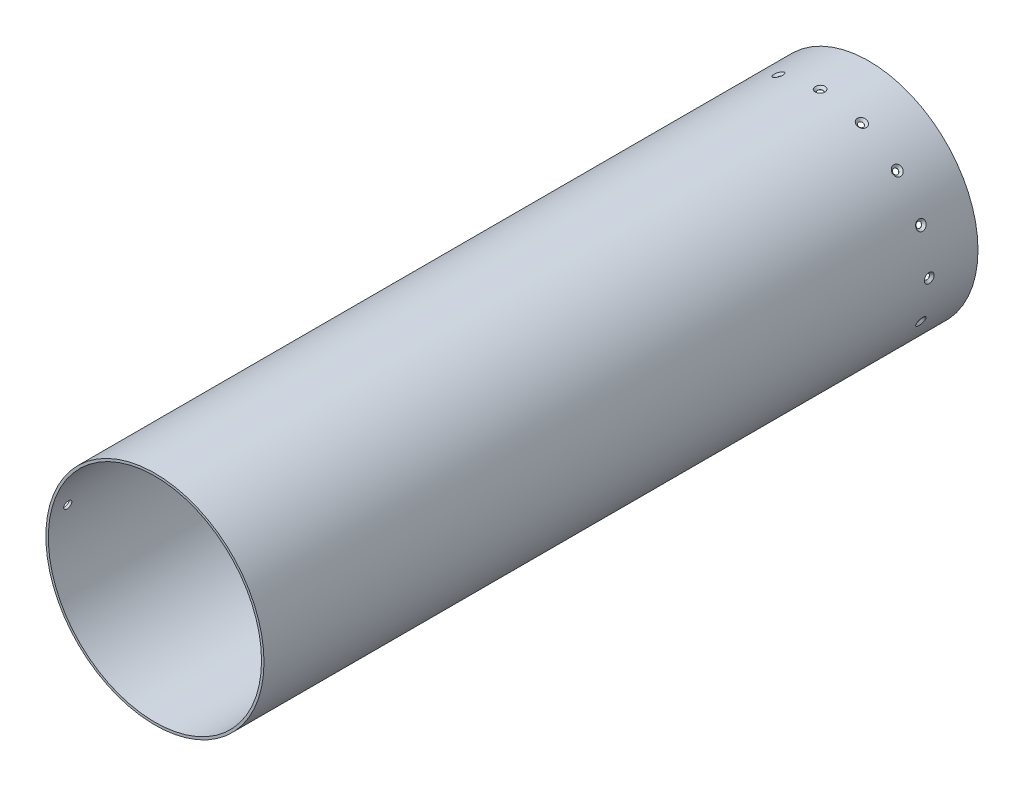
SolidWorks part; units mm, degrees
material "6061-T6 (SS)"
ref_plane "Front Plane" through (0, 0, 0) normal (0, 0, 1) x (1, 0, 0)
ref_plane "Top Plane" through (0, 0, 0) normal (0, 1, 0) x (1, 0, 0)
ref_plane "Right Plane" through (0, 0, 0) normal (1, 0, 0) x (0, 0, -1)
sketch "Sketch1" plane through (0, 0, 0) normal (0, 0, 1) x (1, 0, 0)
  circle A0 centre (0, 0) radius 69.85
  circle A1 centre (0, 0) radius 68.2625
  dimension "D1" = 139.7
  dimension "D2" = 1.5875
extrude "Extrude1" add sketch "Sketch1" along normal blind 457.2
ref_plane "Plane1" through (0, 0, 31.242) normal (0, 0, -1) x (-1, 0, 0)
sketch "Sketch2" plane through (0, 0, 31.242) normal (0, 0, -1) x (-1, 0, 0)
  line L0 (0, 0) -> (0, -69.85) construction
  circle A0 centre (0, 0) radius 69.85 construction
ref_plane "Plane2" through (0, -69.85, 31.242) normal (0, -1, 0) x (1, 0, 0)
hole_wizard "CSK for M3 Flat Head Machine Screw1" positions "Sketch5" profile "Sketch4" countersink size "M3" standard "Ansi Metric" end condition through all
sketch "Sketch5" plane through (0, -69.85, 31.242) normal (0, -1, 0) x (1, 0, 0)
  point P2 (0, 0)
sketch "Sketch4" plane through (0, -69.85, 31.242) normal (1, 0, 0) x (0, 0, -1)
  line L0 (0, 0) -> (0, 161.1134)
  line L1 (0, 161.1134) -> (1.7, 161.1134)
  line L2 (1.7, 161.1134) -> (1.7, 1.45)
  line L3 (1.7, 1.45) -> (3.15, 0)
  line L5 (3.15, 0) -> (0, 0)
  line L6 (-1.7, 1.45) -> (-3.15, 0) construction
  line L11 (0, -6.35) -> (0, 107.95) construction
  dimension "Thru Hole Dia." = 3.4
  dimension "Thru Hole Depth" = 161.1134
  dimension "Near C'Sink Dia." = 6.3
  dimension "Near C'Sink Angle" = 90
pattern_circular "CirPattern1" count 16 over 360 about axis through (0, 0, 457.2) along (0, 0, -1) of "CSK for M3 Flat Head Machine Screw1"
ref_plane "Plane3" through (0, 0, 446.0875) normal (0, 0, 1) x (1, 0, 0)
ref_plane "Plane5" through (0, 0, 0) normal (0.8315, 0.5556, 0) x (-0.5556, 0.8315, 0)
ref_plane "Plane7" through (0, 0, 0) normal (0.5556, -0.8315, 0) x (0.8315, 0.5556, 0)
ref_plane "Plane9" through (0, 0, 0) normal (-0.1951, -0.9808, 0) x (0.9808, -0.1951, 0)
sketch "Sketch7" plane through (0, 0, 457.2) normal (0, 0, 1) x (1, 0, 0)
  circle A0 centre (0, 0) radius 69.85 construction
  point P0 (69.85, 0)
ref_plane "Plane8" through (-68.5079, 13.6271, 228.6) normal (-0.9808, 0.1951, 0) x (0.1951, 0.9808, 0)
sketch "Sketch8" plane through (-68.5079, 13.6271, 228.6) normal (-0.9808, 0.1951, 0) x (0.1951, 0.9808, 0)
  line L1 (-69.85, -228.6) -> (69.85, -228.6) construction
  line L2 (0, -228.6) -> (0, -217.4748) construction
  point P2 (0, -228.6)
  dimension "D1" = 11.1252
hole_wizard "#7 (0.201) Diameter Hole1" positions "Sketch10" profile "Sketch9" hole size "#7" standard "Ansi Inch"
sketch "Sketch10" plane through (-68.5079, 13.6271, 228.6) normal (-0.9808, 0.1951, 0) x (0.1951, 0.9808, 0)
  point P8 (0, -217.4748)
sketch "Sketch9" plane through (-68.5079, 13.6271, 446.0748) normal (0, 0, 1) x (-0.1951, -0.9808, 0)
  line L0 (0, 0) -> (0, 11.6938)
  line L1 (0, 11.6938) -> (2.5527, 10.16)
  line L2 (2.5527, 10.16) -> (2.5527, 0)
  line L5 (2.5527, 0) -> (0, 0)
  line L10 (0, 11.6938) -> (-2.5527, 10.16) construction
  line L11 (0, -6.35) -> (0, 107.95) construction
  dimension "Hole Dia." = 5.1054
  dimension "Hole Depth" = 10.16
  dimension "Drill Angle" = 118
